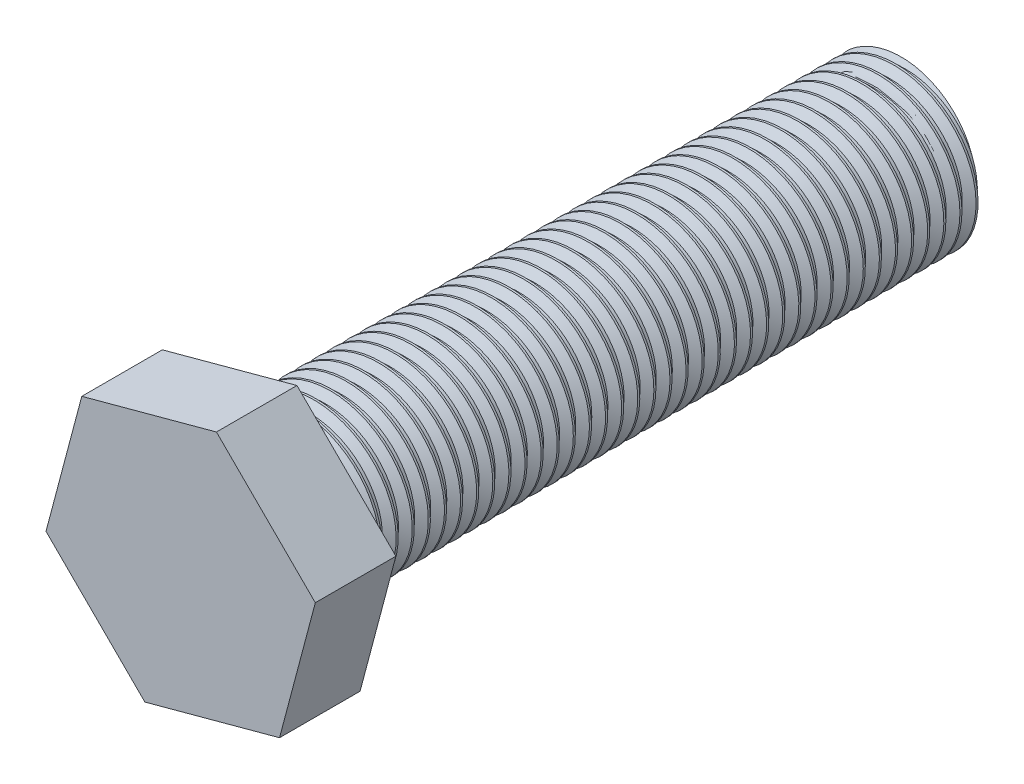
SolidWorks part; units mm, degrees
ref_plane "Front Plane" through (0, 0, 0) normal (0, 0, 1) x (1, 0, 0)
ref_plane "Top Plane" through (0, 0, 0) normal (0, 1, 0) x (1, 0, 0)
ref_plane "Right Plane" through (0, 0, 0) normal (1, 0, 0) x (0, 0, -1)
sketch "Sketch1" plane through (0, 0, 0) normal (0, 0, 1) x (1, 0, 0)
  circle A0 centre (0, 0) radius 6.35
  dimension "D1" = 12.7
extrude "Boss-Extrude1" add sketch "Sketch1" against normal blind 50.8 contours A0
thread "Thread1" pitch 1.27 method cut profile "Thread Profile1" start angle 0, offset 0, length 0, pitch 1.27, diameter 12.7
ref_plane "Plane1" through (-6.35, 0, 0) normal (0, -1, 0) x (-1, 0, 0)
sketch "Thread Profile1" plane through (-6.35, 0, 0) normal (0, -1, 0) x (-1, 0, 0)
  line L0 (0, 0) -> (0, 1.27) construction
  line L11 (0, 0) -> (0, 1.1112)
  line L12 (0, 1.1112) -> (-0.6874, 0.7144)
  line L13 (-0.6874, 0.7144) -> (-0.6874, 0.3969)
  line L15 (-0.6874, 0.3969) -> (0, 0)
  line L17 (-0.6874, 0.5556) -> (0, 0.5556) construction
  point P2 (0, 0)
  dimension "Pitch" = 1.27
  dimension "Profile_Angle" = 60
  dimension "Profile_Land" = 0.3175
  dimension "Profile_Height" = 0.6874
sketch "Sketch8" plane through (0, 0, 0) normal (0, 0, 1) x (1, 0, 0)
  line L1 (10.6169, 2.872) -> (2.8212, 10.6305)
  line L2 (2.8212, 10.6305) -> (-7.7957, 7.7585)
  line L3 (-7.7957, 7.7585) -> (-10.6169, -2.872)
  line L4 (-10.6169, -2.872) -> (-2.8212, -10.6305)
  line L5 (-2.8212, -10.6305) -> (7.7957, -7.7585)
  line L6 (7.7957, -7.7585) -> (10.6169, 2.872)
  circle A0 centre (0, 0) radius 9.525 construction
  dimension "D1" = 19.05
extrude "Boss-Extrude3" add sketch "Sketch8" along normal blind 6.35
